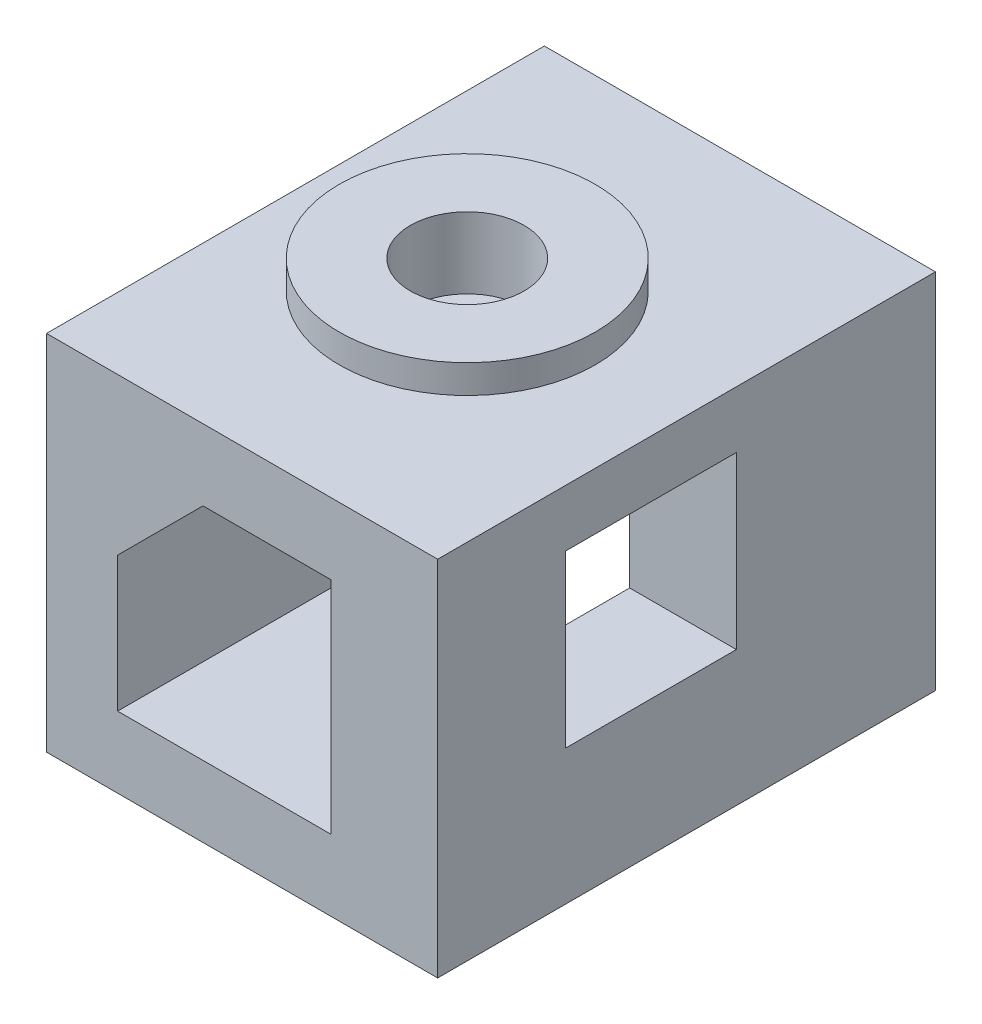
SolidWorks part; units mm, degrees
ref_plane "Front Plane" through (0, 0, 0) normal (0, 0, 1) x (1, 0, 0)
ref_plane "Top Plane" through (0, 0, 0) normal (0, 1, 0) x (1, 0, 0)
ref_plane "Right Plane" through (0, 0, 0) normal (1, 0, 0) x (0, 0, -1)
sketch "Sketch1" plane through (0, 0, 0) normal (0, 0, 1) x (1, 0, 0)
  line L0 (-9.3056, 4.7356) -> (18.1944, 4.7356)
  line L1 (18.1944, 4.7356) -> (18.1944, -0.2644)
  line L2 (18.1944, -0.2644) -> (1.6944, -0.2644)
  line L3 (1.6944, -0.2644) -> (-4.3056, -6.2644)
  line L4 (-4.3056, -6.2644) -> (-4.3056, -13.2644)
  line L5 (-4.3056, -13.2644) -> (-9.3056, -13.2644)
  line L6 (-9.3056, -13.2644) -> (-9.3056, 4.7356)
  line L7 (-4.3056, -6.2644) -> (-4.3056, -0.2644) construction
  line L8 (-4.3056, -0.2644) -> (1.6944, -0.2644) construction
  dimension "D1" = 18
  dimension "D2" = 27.5
  dimension "D3" = 5
  dimension "D4" = 5
  dimension "D5" = 6
  dimension "D6" = 6
extrude "Boss-Extrude1" add sketch "Sketch1" along normal blind 35
sketch "Sketch2" plane through (0, 4.7356, 0) normal (0, 1, 0) x (1, 0, 0)
  line L0 (-9.3056, -35) -> (-9.3056, 0) construction
  line L1 (18.1944, 0) -> (-9.3056, 0) construction
  circle A0 centre (2.9044, -17.63) radius 9
  dimension "D1" = 18
  dimension "D2" = 12.21
  dimension "D3" = 17.63
extrude "Boss-Extrude2" add sketch "Sketch2" along normal blind 2
sketch "Sketch3" plane through (0, 6.7356, 0) normal (0, 1, 0) x (1, 0, 0)
  circle A0 centre (2.9044, -17.63) radius 4
  dimension "D1" = 8
extrude "Cut-Extrude1" cut sketch "Sketch3" against normal blind 5
sketch "Sketch4" plane through (0, -0.2644, 0) normal (0, -1, 0) x (1, 0, 0)
  line L0 (1.6944, 35) -> (18.1944, 35) construction
  line L1 (18.1944, 35) -> (10.6944, 35)
  line L2 (18.1944, 35) -> (18.1944, 0)
  line L3 (18.1944, 0) -> (10.6944, 0)
  line L4 (10.6944, 35) -> (10.6944, 0)
  line L5 (18.1944, 35) -> (18.1944, 0) construction
  line L6 (1.6944, 0) -> (18.1944, 0) construction
  dimension "D1" = 7.5
extrude "Boss-Extrude3" add sketch "Sketch4" along normal blind 20.5
sketch "Sketch6" plane through (18.1944, 0, 0) normal (1, 0, 0) x (0, 0, -1)
  line L0 (-35, 4.7356) -> (0, 4.7356) construction
  line L1 (0, -20.7644) -> (-5, -20.7644)
  line L2 (0, -20.7644) -> (0, 4.7356)
  line L3 (0, 4.7356) -> (-5, 4.7356)
  line L4 (-5, -20.7644) -> (-5, 4.7356)
  dimension "D1" = 5
extrude "Boss-Extrude4" add sketch "Sketch6" along normal blind 7.5 from surface starting at face at (10.6944, -10.5144, 17.5)
sketch "Sketch7" plane through (0, -13.2644, 0) normal (0, -1, 0) x (1, 0, 0)
  line L0 (-4.3056, 35) -> (-4.3056, 0) construction
  line L1 (-9.3056, 35) -> (-4.3056, 35)
  line L2 (-9.3056, 35) -> (-9.3056, 15)
  line L3 (-9.3056, 15) -> (-4.3056, 15)
  line L4 (-4.3056, 35) -> (-4.3056, 15)
  dimension "D1" = 20
extrude "Boss-Extrude5" add sketch "Sketch7" along normal up to surface (7.5 mm away) up to face at (14.4444, -20.7644, 17.5)
sketch "Sketch8" plane through (-4.3056, 0, 0) normal (1, 0, 0) x (0, 0, -1)
  line L0 (-15, -20.7644) -> (-15, -13.2644) construction
  line L1 (-35, -20.7644) -> (-15, -20.7644)
  line L2 (-35, -20.7644) -> (-35, -15.7644)
  line L3 (-35, -15.7644) -> (-15, -15.7644)
  line L4 (-15, -20.7644) -> (-15, -15.7644)
  dimension "D1" = 5
extrude "Boss-Extrude6" add sketch "Sketch8" along normal up to surface (15 mm away) up to face at (10.6944, -10.5144, 17.5)
sketch "Sketch10" plane through (18.1944, 0, 0) normal (1, 0, 0) x (0, 0, -1)
  line L0 (-35, 4.7356) -> (0, 4.7356) construction
  line L1 (-26, 0.7356) -> (-14, 0.7356)
  line L2 (-26, 0.7356) -> (-26, -11.2644)
  line L3 (-26, -11.2644) -> (-14, -11.2644)
  line L4 (-14, 0.7356) -> (-14, -11.2644)
  line L5 (-26, 0.7356) -> (-14, -11.2644) construction
  line L6 (-26, -11.2644) -> (-14, 0.7356) construction
  line L7 (-35, -20.7644) -> (-35, 4.7356) construction
  point P0 (-20, -5.2644)
  dimension "D1" = 12
  dimension "D2" = 12
  dimension "D3" = 10
  dimension "D4" = 15
extrude "Cut-Extrude2" cut sketch "Sketch10" against normal up to surface (7.5 mm away) up to face at (10.6944, -12.2644, 16.6667)
